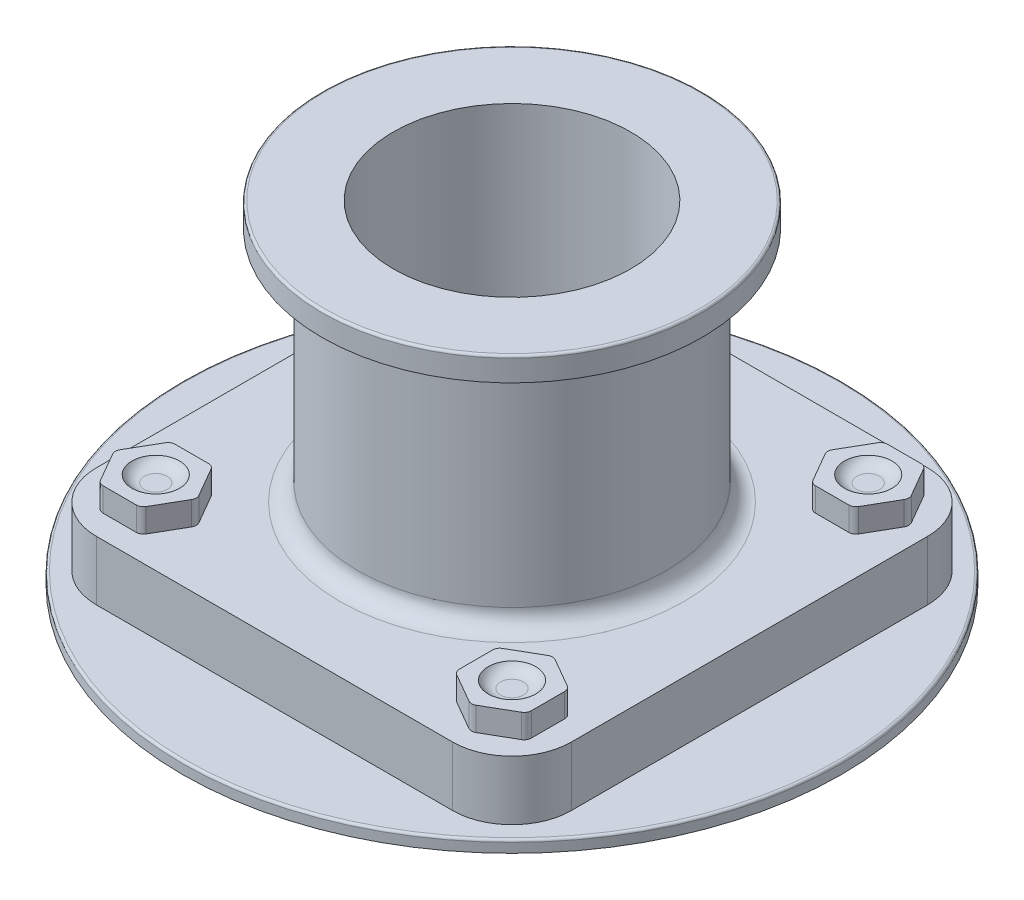
SolidWorks part; units mm, degrees
material "ABS PC"
ref_plane "Front Plane" through (0, 0, 0) normal (0, 0, 1) x (1, 0, 0)
ref_plane "Top Plane" through (0, 0, 0) normal (0, 1, 0) x (1, 0, 0)
ref_plane "Right Plane" through (0, 0, 0) normal (1, 0, 0) x (0, 0, -1)
sketch "Sketch1" plane through (0, 0, 0) normal (0, 1, 0) x (1, 0, 0)
  circle A0 centre (0, 0) radius 277.5
  dimension "D1" = 555
extrude "Boss-Extrude1" add sketch "Sketch1" along normal blind 10
sketch "Sketch2" plane through (0, 10, 0) normal (0, 1, 0) x (1, 0, 0)
  line L1 (200, -200) -> (-200, -200)
  line L2 (200, -200) -> (200, 200)
  line L3 (200, 200) -> (-200, 200)
  line L4 (-200, -200) -> (-200, 200)
  line L5 (200, -200) -> (-200, 200) construction
  line L6 (200, 200) -> (-200, -200) construction
  point P0 (0, 0)
  dimension "D1" = 400
  dimension "D2" = 400
extrude "Boss-Extrude2" add sketch "Sketch2" along normal blind 50
fillet "Fillet1" radius 50 4 edges at (-200, 35, -200) (200, 35, -200) (200, 35, 200) (-200, 35, 200)
sketch "Sketch3" plane through (0, 60, 0) normal (0, 1, 0) x (1, 0, 0)
  circle A0 centre (0, 0) radius 130
  dimension "D1" = 260
extrude "Boss-Extrude3" add sketch "Sketch3" along normal blind 200
sketch "Sketch4" plane through (0, 260, 0) normal (0, 1, 0) x (1, 0, 0)
  circle A0 centre (0, 0) radius 160
  dimension "D1" = 320
extrude "Boss-Extrude4" add sketch "Sketch4" along normal blind 20
sketch "Sketch7" plane through (0, 280, 0) normal (0, 1, 0) x (1, 0, 0)
  circle A0 centre (0, 0) radius 100
  dimension "D1" = 200
extrude "Cut-Extrude2" cut sketch "Sketch7" against normal blind 200
fillet "Fillet3" radius 15 1 edges at (0, 60, 130)
fillet "Fillet4" radius 2 2 edges at (0, 10, 277.5) (0, 280, 160)
sketch "Sketch8" plane through (0, 60, 0) normal (0, 1, 0) x (1, 0, 0)
  line L0 (-150, -200) -> (150, -200) construction
  line L1 (150, -185) -> (180.3109, -167.5)
  line L2 (180.3109, -167.5) -> (180.3109, -132.5)
  line L3 (180.3109, -132.5) -> (150, -115)
  line L4 (150, -115) -> (119.6891, -132.5)
  line L5 (119.6891, -132.5) -> (119.6891, -167.5)
  line L6 (119.6891, -167.5) -> (150, -185)
  line L7 (200, -150) -> (200, 150) construction
  circle A0 centre (150, -150) radius 30.3109 construction
  dimension "D1" = 35
  dimension "D2" = 50
  dimension "D3" = 50
extrude "Boss-Extrude6" add sketch "Sketch8" along normal blind 20
sketch "Sketch9" plane through (0, 80, 0) normal (0, 1, 0) x (1, 0, 0)
  circle A0 centre (150, -150) radius 20
  dimension "D1" = 40
extrude "Cut-Extrude3" cut sketch "Sketch9" against normal blind 6
fillet "Fillet5" radius 12 1 edges at (150, 74, 170)
fillet "Fillet6" radius 6 6 edges at (119.6891, 70, 167.5) (119.6891, 70, 132.5) (150, 70, 115) (180.3109, 70, 132.5) (150, 70, 185) (180.3109, 70, 167.5)
pattern_circular "CirPattern1" count 4 over 360 about axis through (0, 260, 0) along (0, -1, 0) of "Boss-Extrude6", "Fillet5", "Cut-Extrude3", "Fillet6" reverse direction yes
